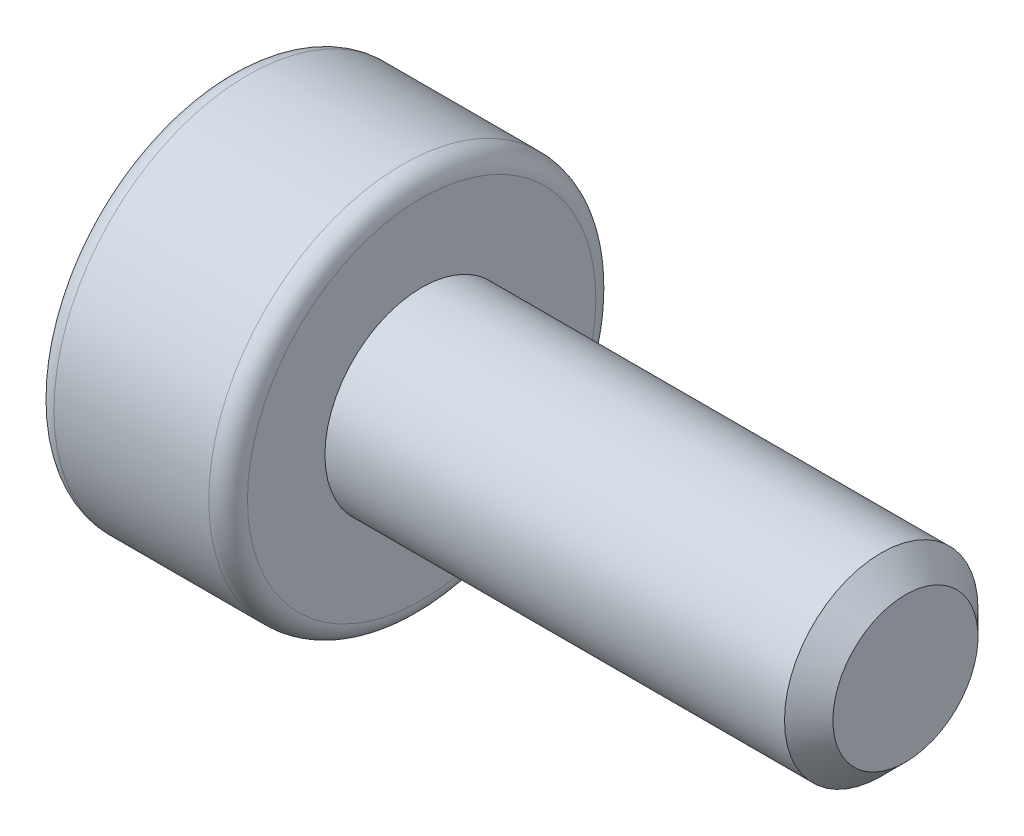
SolidWorks part; units mm, degrees
ref_plane "Front Plane" through (0, 0, 0) normal (0, 0, 1) x (1, 0, 0)
ref_plane "Top Plane" through (0, 0, 0) normal (0, 1, 0) x (1, 0, 0)
ref_plane "Right Plane" through (0, 0, 0) normal (1, 0, 0) x (0, 0, -1)
sketch "Sketch2" plane through (0, 0, 0) normal (0, 0, 1) x (1, 0, 0)
  line L0 (0, 0) -> (0, 1.8)
  line L1 (2, 1) -> (2, 1.8)
  line L2 (1.8, 2) -> (0.2, 2)
  line L3 (2, 1) -> (6.75, 1)
  line L4 (6.75, 1) -> (7, 0.75)
  line L5 (7, 0.75) -> (7, 0)
  line L6 (7, 0) -> (0, 0)
  line L7 (-2.2818, 0) -> (8.0811, 0) construction
  arc A0 (2, 1.8) -> (1.8, 2) centre (1.8, 1.8) ccw
  arc A1 (0, 1.8) -> (0.2, 2) centre (0.2, 1.8) cw
  point P4 (6.7074, 1)
  point P13 (2, 2)
  point P16 (0, 2)
  dimension "D7" = 0.2
  dimension "D1" = 4
  dimension "D2" = 2
  dimension "D3" = 5
  dimension "D4" = 135
  dimension "D5" = 0.25
  dimension "D6" = 2
revolve "Revolve1" add sketch "Sketch2" angle 360 about L7
sketch "Sketch3" plane through (0, 0, 0) normal (-1, 0, 0) x (0, 0, 1)
  line L1 (0.433, -0.75) -> (0.866, 0)
  line L2 (0.866, 0) -> (0.433, 0.75)
  line L3 (0.433, 0.75) -> (-0.433, 0.75)
  line L4 (-0.433, 0.75) -> (-0.866, 0)
  line L5 (-0.866, 0) -> (-0.433, -0.75)
  line L6 (-0.433, -0.75) -> (0.433, -0.75)
  circle A0 centre (0, 0) radius 0.75 construction
  dimension "D1" = 1.5
extrude "Cut-Extrude1" cut sketch "Sketch3" against normal blind 0.8
